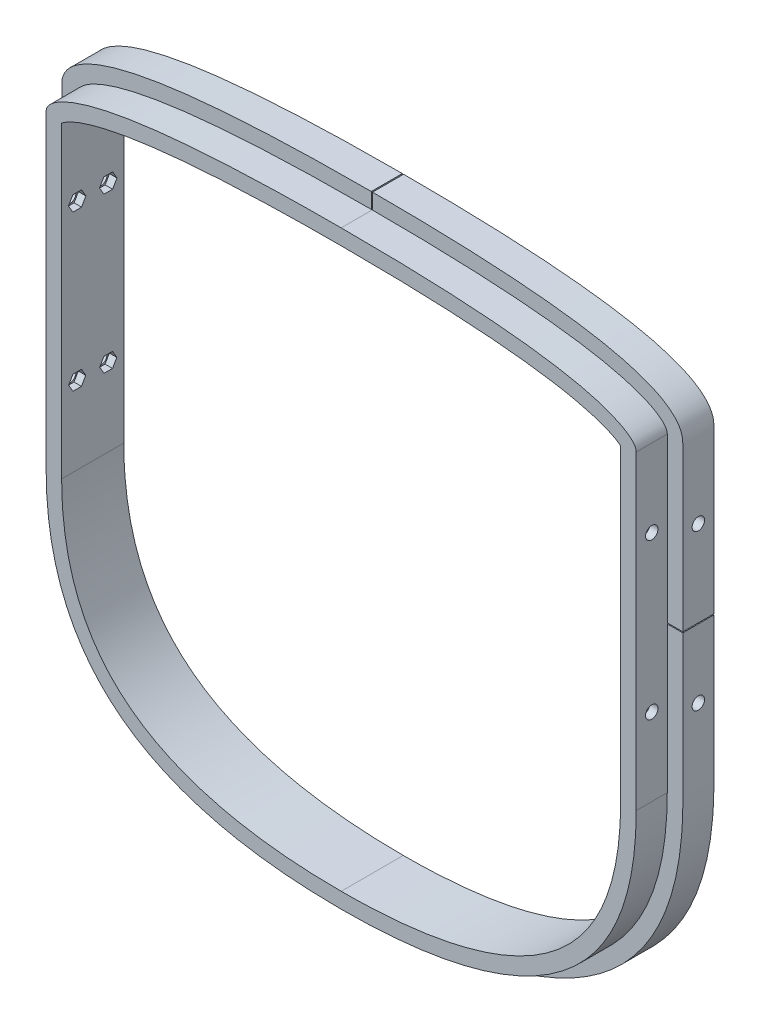
SolidWorks part; units mm, degrees
ref_plane "Front Plane" through (0, 0, 0) normal (0, 0, 1) x (1, 0, 0)
ref_plane "Top Plane" through (0, 0, 0) normal (0, 1, 0) x (1, 0, 0)
ref_plane "Right Plane" through (0, 0, 0) normal (1, 0, 0) x (0, 0, -1)
sketch "Sketch1" plane through (0, 0, 0) normal (0, 0, 1) x (1, 0, 0)
  line L0 (-95, 0) -> (-95, 100) construction
  line L1 (95, 100) -> (95, 0) construction
  line L2 (-95, 0) -> (-95, 100)
  line L3 (95, 100) -> (95, 0)
  line L4 (90, 99.1825) -> (90, 0)
  line L5 (-90, 0) -> (-90, 99.1825)
  line L15 (0.1, -75.1462) -> (-0.3, -75.1462)
  line L16 (-95.145, 47.3605) -> (-95.145, 47.0605)
  line L17 (-100.005, 47.3605) -> (-95.145, 47.3605)
  line L18 (-95.145, 47.0605) -> (-100.005, 47.0605)
  line L19 (-95.145, 47.3605) -> (-95.145, 47.0605)
  line L20 (-100.005, 47.3605) -> (-95.145, 47.3605)
  line L21 (-95.145, 47.0605) -> (-100.005, 47.0605)
  line L22 (-0.3, -75.1462) -> (-0.3, -80.0059)
  line L23 (0.1, -80.006) -> (0.1, -75.1462)
  line L24 (0.1, -75.1462) -> (-0.3, -75.1462)
  line L25 (-0.3, -75.1462) -> (-0.3, -80.0059)
  line L26 (0.1, -80.006) -> (0.1, -75.1462)
  line L28 (-0.3, 115.1456) -> (-0.3, 120.0054)
  line L29 (0.1, 115.1456) -> (-0.3, 115.1456)
  line L30 (0.1, 120.0054) -> (0.1, 115.1456)
  line L31 (-0.3, 115.1456) -> (-0.3, 120.0054)
  line L32 (0.1, 115.1456) -> (-0.3, 115.1456)
  line L33 (0.1, 120.0054) -> (0.1, 115.1456)
  line L41 (95.145, 47.3605) -> (95.145, 47.0605)
  line L42 (95.145, 47.0605) -> (100.005, 47.0605)
  line L43 (100.005, 47.3605) -> (95.145, 47.3605)
  line L44 (95.145, 47.3605) -> (95.145, 47.0605)
  line L45 (95.145, 47.0605) -> (100.005, 47.0605)
  line L46 (100.005, 47.3605) -> (95.145, 47.3605)
  spline S1 degree 3 poles (3136.7113, -2595.1283) (-411.3752, 491.0799) (124.7191, 163.024) (92.6225, -23.0563) (91.0727, -28.5917) (87.718, -36.376) (86.4275, -38.8874) (83.5045, -43.6754) (81.8668, -45.9605) (78.2726, -50.2518) (76.3088, -52.2667) (72.1059, -55.9971) (69.8602, -57.7184) (62.7901, -62.4376) (57.6248, -64.994) (46.8118, -69.0969) (41.1658, -70.649) (29.6492, -72.9887) (23.7792, -73.7773) (-231.7054, -95.489) (-565.5671, 391.7896) (1436.1298, -3777.9141) knots -3.843615 -3.843615 -3.843615 -3.843615 0.125 0.125 0.25 0.25 0.3125 0.3125 0.375 0.375 0.4375 0.4375 0.5 0.5 0.625 0.625 0.75 0.75 0.875 0.875 6.146969 6.146969 6.146969 6.146969 only from (95, 0) to (0, -75) construction
  spline S2 degree 3 poles (-1436.1603, -3777.9993) (565.5714, 391.7943) (231.7065, -95.4891) (-23.7792, -73.7773) (-29.6492, -72.9887) (-41.1658, -70.649) (-46.8118, -69.0969) (-57.6248, -64.994) (-62.7901, -62.4376) (-69.8602, -57.7184) (-72.1059, -55.9971) (-76.3088, -52.2667) (-78.2726, -50.2518) (-81.8668, -45.9605) (-83.5045, -43.6754) (-86.4275, -38.8874) (-87.718, -36.376) (-91.0727, -28.5917) (-92.6225, -23.0563) (-94.0926, -14.5332) (-94.4416, -11.6547) (-94.7819, -7.3036) (-94.9425, -4.4835) (-94.9966, -1.6488) (-95.0143, 6.252) (-94.5075, -6.0366) (-93.6764, 3996.2013) knots -5.146991 -5.146991 -5.146991 -5.146991 0.125 0.125 0.25 0.25 0.375 0.375 0.5 0.5 0.5625 0.5625 0.625 0.625 0.6875 0.6875 0.75 0.75 0.875 0.875 0.9375 0.9375 0.96875 0.998047 0.998047 1.137215 1.137215 1.137215 1.137215 only from (0, -75) to (-95, 0) construction
  spline S3 degree 3 poles (1746.8759, 3647.4615) (-23.1446, -17.0755) (-97.5608, 88.6601) (-94.9009, 100.7509) (-94.8371, 100.9436) (-94.5702, 101.5255) (-94.2605, 101.9807) (-93.3234, 102.955) (-92.7294, 103.4423) (-91.3279, 104.396) (-90.5529, 104.8424) (-88.041, 106.1129) (-86.1831, 106.8394) (-82.3083, 108.1222) (-80.2973, 108.6758) (-74.1487, 110.1566) (-69.9126, 110.9055) (-61.3553, 112.1444) (-57.0295, 112.63) (-48.336, 113.4313) (-43.9687, 113.7455) (-35.2116, 114.2529) (-30.8224, 114.4456) (338.3636, 126.7888) (742.3965, -171.5462) (163.6137, 3990.1333) knots -1.04491 -1.04491 -1.04491 -1.04491 0.015625 0.015625 0.03125 0.03125 0.0625 0.0625 0.09375 0.09375 0.125 0.125 0.1875 0.1875 0.25 0.25 0.375 0.375 0.5 0.5 0.625 0.625 0.75 0.75 11.124038 11.124038 11.124038 11.124038 only from (-95, 100) to (0, 115) construction
  spline S4 degree 3 poles (-163.1607, 3990.1804) (-742.4074, -171.5484) (-338.3648, 126.7888) (30.8224, 114.4456) (35.2116, 114.2529) (43.9687, 113.7455) (48.336, 113.4313) (57.0295, 112.63) (61.3553, 112.1444) (69.9126, 110.9055) (74.1487, 110.1566) (80.2973, 108.6758) (82.3083, 108.1222) (86.1831, 106.8394) (88.041, 106.1129) (90.5529, 104.8424) (91.3279, 104.396) (92.7294, 103.4423) (93.3234, 102.955) (94.2605, 101.9807) (94.5702, 101.5255) (94.8371, 100.9436) (94.9009, 100.7509) (94.9588, 100.4876) (94.974, 100.3949) (94.9895, 100.2502) (94.9971, 100.1551) (94.9998, 100.0573) (95.0006, 99.8105) (94.9809, 121.0154) (94.9385, -3853.5047) knots -10.124077 -10.124077 -10.124077 -10.124077 0.25 0.25 0.375 0.375 0.5 0.5 0.625 0.625 0.75 0.75 0.8125 0.8125 0.875 0.875 0.90625 0.90625 0.9375 0.9375 0.96875 0.96875 0.984375 0.984375 0.992187 0.992187 0.996094 0.999756 0.999756 1.015024 1.015024 1.015024 1.015024 only from (0, 115) to (95, 100) construction
  spline S5 degree 3 poles (95, 0) (95, -5.8637) (94.5826, -11.6922) (92.6225, -23.0563) (91.0727, -28.5917) (87.718, -36.376) (86.4275, -38.8874) (83.5045, -43.6754) (81.8668, -45.9605) (78.2726, -50.2518) (76.3088, -52.2667) (72.1059, -55.9971) (69.8602, -57.7184) (62.7901, -62.4376) (57.6248, -64.994) (46.8118, -69.0969) (41.1658, -70.649) (29.6492, -72.9887) (23.7792, -73.7773) (11.9445, -74.783) (5.9798, -75) (0, -75) knots 0 0 0 0 0.125 0.125 0.25 0.25 0.3125 0.3125 0.375 0.375 0.4375 0.4375 0.5 0.5 0.625 0.625 0.75 0.75 0.875 0.875 1 1 1 1
  spline S6 degree 3 poles (0, -75) (-5.9798, -75) (-11.9445, -74.783) (-23.7792, -73.7773) (-29.6492, -72.9887) (-41.1658, -70.649) (-46.8118, -69.0969) (-57.6248, -64.994) (-62.7901, -62.4376) (-69.8602, -57.7184) (-72.1059, -55.9971) (-76.3088, -52.2667) (-78.2726, -50.2518) (-81.8668, -45.9605) (-83.5045, -43.6754) (-86.4275, -38.8874) (-87.718, -36.376) (-91.0727, -28.5917) (-92.6225, -23.0563) (-94.0926, -14.5332) (-94.4416, -11.6547) (-94.7819, -7.3036) (-94.9425, -4.4835) (-94.9966, -1.6488) (-94.9999, -0.1832) (-95, -0.0953) (-95, 0) knots 0 0 0 0 0.125 0.125 0.25 0.25 0.375 0.375 0.5 0.5 0.5625 0.5625 0.625 0.625 0.6875 0.6875 0.75 0.75 0.875 0.875 0.9375 0.9375 0.96875 0.998047 0.998047 1 1 1 1
  spline S7 degree 3 poles (-95, 100) (-95, 100.2039) (-94.9781, 100.3998) (-94.9009, 100.7509) (-94.8371, 100.9436) (-94.5702, 101.5255) (-94.2605, 101.9807) (-93.3234, 102.955) (-92.7294, 103.4423) (-91.3279, 104.396) (-90.5529, 104.8424) (-88.041, 106.1129) (-86.1831, 106.8394) (-82.3083, 108.1222) (-80.2973, 108.6758) (-74.1487, 110.1566) (-69.9126, 110.9055) (-61.3553, 112.1444) (-57.0295, 112.63) (-48.336, 113.4313) (-43.9687, 113.7455) (-35.2116, 114.2529) (-30.8224, 114.4456) (-17.636, 114.8864) (-8.8222, 115) (0, 115) knots 0 0 0 0 0.015625 0.015625 0.03125 0.03125 0.0625 0.0625 0.09375 0.09375 0.125 0.125 0.1875 0.1875 0.25 0.25 0.375 0.375 0.5 0.5 0.625 0.625 0.75 0.75 1 1 1 1
  spline S8 degree 3 poles (0, 115) (8.8222, 115) (17.636, 114.8864) (30.8224, 114.4456) (35.2116, 114.2529) (43.9687, 113.7455) (48.336, 113.4313) (57.0295, 112.63) (61.3553, 112.1444) (69.9126, 110.9055) (74.1487, 110.1566) (80.2973, 108.6758) (82.3083, 108.1222) (86.1831, 106.8394) (88.041, 106.1129) (90.5529, 104.8424) (91.3279, 104.396) (92.7294, 103.4423) (93.3234, 102.955) (94.2605, 101.9807) (94.5702, 101.5255) (94.8371, 100.9436) (94.9009, 100.7509) (94.9588, 100.4876) (94.974, 100.3949) (94.9895, 100.2502) (94.9971, 100.1551) (94.9998, 100.0573) (95, 100.0064) (95, 100.0087) (95, 100) knots 0 0 0 0 0.25 0.25 0.375 0.375 0.5 0.5 0.625 0.625 0.75 0.75 0.8125 0.8125 0.875 0.875 0.90625 0.90625 0.9375 0.9375 0.96875 0.96875 0.984375 0.984375 0.992187 0.992187 0.996094 0.999756 0.999756 1 1 1 1
  spline S9 degree 1 poles (0, 110) (90, 99.1825) knots 0 0 1 1 construction
  spline S10 degree 1 poles (90, 0) (0, -70) knots 0 0 1 1 construction
  spline S11 degree 1 poles (0, -70) (-90, 0) knots 0 0 1 1 construction
  spline S12 degree 1 poles (-90, 99.1825) (0, 110) knots 0 0 1 1 construction
  spline S13 degree 3 poles (0, 110) (8.1276, 110) (20.3516, 109.8536) (36.5125, 109.2102) (48.5534, 108.436) (58.4634, 107.4683) (66.2506, 106.4099) (71.9725, 105.4481) (76.5934, 104.4569) (80.131, 103.5305) (82.6718, 102.757) (85.0595, 101.9021) (86.8381, 101.1276) (88.0895, 100.4819) (88.8949, 100.0077) (89.4525, 99.6267) (89.8035, 99.3531) (89.9322, 99.2434) (90, 99.1825) knots 0 0 0 0 0.232049 0.348073 0.464097 0.580122 0.638134 0.696146 0.754158 0.783164 0.81217 0.841177 0.870183 0.884686 0.899189 0.913692 0.920943 0.928195 0.928195 0.928195 0.928195
  spline S14 degree 3 poles (90, 0) (90, -1.4013) (89.9499, -4.2123) (89.6338, -9.7605) (88.8063, -16.5742) (87.0275, -24.4516) (83.521, -34.3766) (76.8406, -45.3886) (65.1997, -55.6458) (50.7269, -62.8249) (34.5596, -67.2786) (20.3492, -69.1916) (8.7749, -69.8937) (2.9198, -70) (0, -70) knots 0 0 0 0 0.03125 0.0625 0.125 0.1875 0.25 0.375 0.5 0.625 0.75 0.875 0.9375 1 1 1 1
  spline S15 degree 3 poles (0, -70) (-2.9198, -70) (-8.7749, -69.8937) (-20.3492, -69.1916) (-34.5596, -67.2786) (-50.7269, -62.8249) (-65.1997, -55.6458) (-76.8406, -45.3885) (-83.5211, -34.3767) (-87.0274, -24.4515) (-88.8064, -16.5747) (-89.6333, -9.759) (-89.9498, -4.211) (-90, -1.4009) (-90, 0) knots 0 0 0 0 0.0625 0.125 0.25 0.375 0.5 0.625 0.75 0.8125 0.875 0.9375 0.96875 1 1 1 1
  spline S16 degree 3 poles (-90, 99.1825) (-89.9322, 99.2434) (-89.8035, 99.3531) (-89.4525, 99.6267) (-88.8949, 100.0077) (-88.0895, 100.4819) (-86.8381, 101.1276) (-85.0595, 101.9021) (-82.6718, 102.757) (-80.131, 103.5305) (-76.5934, 104.4569) (-71.9725, 105.4481) (-66.2506, 106.4099) (-58.4634, 107.4683) (-48.5534, 108.436) (-36.5125, 109.2102) (-20.3516, 109.8536) (-8.1276, 110) (0, 110) knots 0.071805 0.071805 0.071805 0.071805 0.079057 0.086308 0.100811 0.115314 0.129817 0.158823 0.18783 0.216836 0.245842 0.303854 0.361866 0.419878 0.535903 0.651927 0.767951 1 1 1 1
  spline S18 degree 3 poles (89.2894, -43.9961) (91.0924, -40.6251) (91.1479, -40.5206) (91.2571, -40.3137) (91.42, -40.003) (91.7934, -39.276) (92.1023, -38.6495) (92.7058, -37.3919) (93.0889, -36.5476) (94.1838, -33.998) (94.8411, -32.2758) (96.6159, -27.0485) (97.5366, -23.4826) (98.5817, -18.0301) (98.8743, -16.1936) (99.3549, -12.496) (99.5418, -10.6463) (99.8198, -6.9456) (99.9107, -5.0945) (99.9818, -2.3169) (99.9946, -1.3908) (100.004, 0.4615) (100.0008, 1.3878) (99.9972, 4.1666) (99.9995, 6.019) (100.0011, 9.724) (100.0011, 11.5764) (100.0003, 17.1339) (99.9994, 20.8388) (99.9991, 31.9537) (100.0002, 39.3636) (100.0008, 61.5933) (99.9994, 76.4132) (100.0001, 93.0855) (100.0002, 94.9379) (99.9998, 97.7166) (100.0006, 98.6429) (99.9999, 99.8007) (100.0031, 100.0323) (99.9877, 100.4953) (99.9698, 100.7277) (99.8853, 101.4154) (99.7878, 101.8625) (99.5813, 102.5168) (99.5026, 102.7322) (99.3259, 103.1577) (99.2273, 103.3688) (98.9092, 103.9833) (98.6676, 104.3702) (98.1354, 105.1066) (97.8446, 105.4557) (97.2218, 106.1225) (96.8891, 106.4419) (95.8513, 107.3516) (95.1114, 107.8916) (93.9523, 108.6336) (93.5566, 108.8696) (92.7564, 109.32) (92.352, 109.5348) (90.3124, 110.5653) (88.6243, 111.2523) (85.1828, 112.4675) (83.4252, 112.9926) (79.8891, 113.9339) (78.1085, 114.3523) (74.5282, 115.1082) (72.7277, 115.4458) (67.3202, 116.3691) (63.7018, 116.8707) (56.4467, 117.7168) (52.8099, 118.0606) (45.5242, 118.6449) (41.8739, 118.8861) (34.5781, 119.2834) (30.931, 119.4408) (19.9911, 119.8193) (12.7001, 119.9439) (1.7659, 120.0061) (-1.8785, 120.0058) (-9.1666, 119.9636) (-12.8102, 119.9212) (-23.7398, 119.717) (-31.0244, 119.4775) (-41.9471, 118.8809) (-45.5873, 118.6424) (-52.8658, 118.0566) (-56.5041, 117.7079) (-61.9594, 117.0693) (-63.7791, 116.8375) (-67.4067, 116.3266) (-69.2149, 116.0472) (-72.8175, 115.4287) (-74.6122, 115.091) (-78.1833, 114.3362) (-79.9595, 113.9188) (-83.4862, 112.9727) (-85.2374, 112.4474) (-87.8337, 111.5274) (-88.694, 111.1988) (-90.4015, 110.4845) (-91.2418, 110.1007) (-92.8816, 109.2645) (-93.6826, 108.8131) (-94.8397, 108.0582) (-95.2179, 107.7936) (-95.9574, 107.2344) (-96.3198, 106.9397) (-97.3571, 106.0156) (-97.986, 105.3409) (-98.6504, 104.3835) (-98.777, 104.186) (-99.0122, 103.7852) (-99.1214, 103.5811) (-99.4226, 102.9575) (-99.5886, 102.5267) (-99.7789, 101.8551) (-99.8326, 101.6257) (-99.9172, 101.1674) (-99.9483, 100.9377) (-100.0087, 100.247) (-100.0052, 99.7843) (-99.9986, 98.859) (-100, 98.3965) (-100.0004, 97.4715) (-99.9999, 97.0091) (-100.0002, 94.6966) (-100, 92.8466) (-100, 87.2967) (-100, 76.1969) (-100, 65.0971) (-100, 42.8974) (-100, 28.0976) (-100, 9.5979) (-99.9994, 5.898) (-100, 1.2731) (-100.0018, 0.3481) (-99.9938, -1.5019) (-99.9804, -2.4272) (-99.9053, -5.1961) (-99.8127, -7.0353) (-99.3966, -12.5309) (-98.9349, -16.1653) (-97.5636, -23.3627) (-96.6555, -26.926) (-94.8697, -32.2035) (-94.2095, -33.9324) (-92.7581, -37.3147) (-91.9659, -38.9698) (-89.3854, -43.825) (-87.3956, -46.916) (-84.5253, -50.5724) (-83.9342, -51.29) (-82.7265, -52.6889) (-82.1088, -53.3719) (-80.2156, -55.3732) (-78.9002, -56.6439) (-74.8049, -60.2787) (-71.8763, -62.4655) (-67.9847, -64.9244) (-67.1949, -65.4025) (-65.5931, -66.3322) (-64.7811, -66.7836) (-62.3319, -68.0889) (-60.6753, -68.8977) (-55.6412, -71.1595) (-52.2001, -72.4492) (-46.9351, -74.1184) (-45.1627, -74.63) (-42.4801, -75.3361) (-41.5819, -75.5613) (-39.7868, -75.99) (-38.8889, -76.1938) (-34.3969, -77.1637) (-30.7968, -77.783) (-23.5862, -78.7748) (-19.9756, -79.1464) (-12.746, -79.6872) (-9.1268, -79.8545) (-1.8815, -80.0215) (1.7446, -80.024) (9.0038, -79.861) (12.6371, -79.6936) (19.9122, -79.1523) (23.5541, -78.7785) (30.8488, -77.7749) (34.4618, -77.1502) (41.6046, -75.6052) (45.1347, -74.6856) (52.094, -72.4867) (55.5231, -71.2071) (59.7297, -69.3235) (60.5684, -68.9318) (62.2292, -68.1218) (63.0509, -67.7037) (65.489, -66.4087) (67.0786, -65.4911) (71.7327, -62.565) (74.6828, -60.3835) (78.1475, -57.3194) (78.8291, -56.6896) (80.156, -55.4072) (80.8029, -54.7532) (82.6937, -52.7522) (83.8881, -51.3668) (87.2805, -47.0622) (89.2894, -43.9961) (91.0924, -40.6251) (91.1479, -40.5206) knots -0.015625 -0.015625 0 0 0.000488 0.000488 0.000977 0.001953 0.003906 0.003906 0.007812 0.007812 0.015625 0.015625 0.03125 0.03125 0.039062 0.039062 0.046875 0.046875 0.054687 0.054687 0.058594 0.058594 0.0625 0.0625 0.070312 0.070312 0.078125 0.078125 0.09375 0.09375 0.125 0.125 0.1875 0.1875 0.195312 0.195312 0.199219 0.199219 0.200195 0.200195 0.201172 0.201172 0.203125 0.203125 0.204102 0.204102 0.205078 0.205078 0.207031 0.207031 0.208984 0.208984 0.210937 0.210937 0.214844 0.214844 0.216797 0.216797 0.21875 0.21875 0.226562 0.226562 0.234375 0.234375 0.242187 0.242187 0.25 0.25 0.265625 0.265625 0.28125 0.28125 0.296875 0.296875 0.3125 0.3125 0.34375 0.34375 0.359375 0.359375 0.375 0.375 0.40625 0.40625 0.421875 0.421875 0.4375 0.4375 0.445312 0.445312 0.453125 0.453125 0.460937 0.460937 0.46875 0.46875 0.476562 0.476562 0.480469 0.480469 0.484375 0.484375 0.488281 0.488281 0.490234 0.490234 0.492187 0.492187 0.496094 0.496094 0.49707 0.49707 0.498047 0.498047 0.5 0.5 0.500977 0.500977 0.501953 0.501953 0.503906 0.503906 0.505859 0.505859 0.507812 0.507812 0.515625 0.515625 0.53125 0.5625 0.5625 0.625 0.625 0.640625 0.640625 0.644531 0.644531 0.648437 0.648437 0.65625 0.65625 0.671875 0.671875 0.6875 0.6875 0.695312 0.695312 0.703125 0.703125 0.71875 0.71875 0.722656 0.722656 0.726562 0.726562 0.734375 0.734375 0.75 0.75 0.753906 0.753906 0.757812 0.757812 0.765625 0.765625 0.78125 0.78125 0.789062 0.789062 0.792969 0.792969 0.796875 0.796875 0.8125 0.8125 0.828125 0.828125 0.84375 0.84375 0.859375 0.859375 0.875 0.875 0.890625 0.890625 0.90625 0.90625 0.921875 0.921875 0.9375 0.9375 0.941406 0.941406 0.945312 0.945312 0.953125 0.953125 0.96875 0.96875 0.972656 0.972656 0.976562 0.976562 0.984375 0.984375 1 1 1.000488 1.000488 1.000977 only from (91.0378, -40.7273) to (91.0378, -40.7273)
  spline S19 degree 3 poles (89.2894, -43.9961) (91.0924, -40.6251) (91.1479, -40.5206) (91.2571, -40.3137) (91.42, -40.003) (91.7934, -39.276) (92.1023, -38.6495) (92.7058, -37.3919) (93.0889, -36.5476) (94.1838, -33.998) (94.8411, -32.2758) (96.6159, -27.0485) (97.5366, -23.4826) (98.5817, -18.0301) (98.8743, -16.1936) (99.3549, -12.496) (99.5418, -10.6463) (99.8198, -6.9456) (99.9107, -5.0945) (99.9818, -2.3169) (99.9946, -1.3908) (100.004, 0.4615) (100.0008, 1.3878) (99.9972, 4.1666) (99.9995, 6.019) (100.0011, 9.724) (100.0011, 11.5764) (100.0003, 17.1339) (99.9994, 20.8388) (99.9991, 31.9537) (100.0002, 39.3636) (100.0008, 61.5933) (99.9994, 76.4132) (100.0001, 93.0855) (100.0002, 94.9379) (99.9998, 97.7166) (100.0006, 98.6429) (99.9999, 99.8007) (100.0031, 100.0323) (99.9877, 100.4953) (99.9698, 100.7277) (99.8853, 101.4154) (99.7878, 101.8625) (99.5813, 102.5168) (99.5026, 102.7322) (99.3259, 103.1577) (99.2273, 103.3688) (98.9092, 103.9833) (98.6676, 104.3702) (98.1354, 105.1066) (97.8446, 105.4557) (97.2218, 106.1225) (96.8891, 106.4419) (95.8513, 107.3516) (95.1114, 107.8916) (93.9523, 108.6336) (93.5566, 108.8696) (92.7564, 109.32) (92.352, 109.5348) (90.3124, 110.5653) (88.6243, 111.2523) (85.1828, 112.4675) (83.4252, 112.9926) (79.8891, 113.9339) (78.1085, 114.3523) (74.5282, 115.1082) (72.7277, 115.4458) (67.3202, 116.3691) (63.7018, 116.8707) (56.4467, 117.7168) (52.8099, 118.0606) (45.5242, 118.6449) (41.8739, 118.8861) (34.5781, 119.2834) (30.931, 119.4408) (19.9911, 119.8193) (12.7001, 119.9439) (1.7659, 120.0061) (-1.8785, 120.0058) (-9.1666, 119.9636) (-12.8102, 119.9212) (-23.7398, 119.717) (-31.0244, 119.4775) (-41.9471, 118.8809) (-45.5873, 118.6424) (-52.8658, 118.0566) (-56.5041, 117.7079) (-61.9594, 117.0693) (-63.7791, 116.8375) (-67.4067, 116.3266) (-69.2149, 116.0472) (-72.8175, 115.4287) (-74.6122, 115.091) (-78.1833, 114.3362) (-79.9595, 113.9188) (-83.4862, 112.9727) (-85.2374, 112.4474) (-87.8337, 111.5274) (-88.694, 111.1988) (-90.4015, 110.4845) (-91.2418, 110.1007) (-92.8816, 109.2645) (-93.6826, 108.8131) (-94.8397, 108.0582) (-95.2179, 107.7936) (-95.9574, 107.2344) (-96.3198, 106.9397) (-97.3571, 106.0156) (-97.986, 105.3409) (-98.6504, 104.3835) (-98.777, 104.186) (-99.0122, 103.7852) (-99.1214, 103.5811) (-99.4226, 102.9575) (-99.5886, 102.5267) (-99.7789, 101.8551) (-99.8326, 101.6257) (-99.9172, 101.1674) (-99.9483, 100.9377) (-100.0087, 100.247) (-100.0052, 99.7843) (-99.9986, 98.859) (-100, 98.3965) (-100.0004, 97.4715) (-99.9999, 97.0091) (-100.0002, 94.6966) (-100, 92.8466) (-100, 87.2967) (-100, 76.1969) (-100, 65.0971) (-100, 42.8974) (-100, 28.0976) (-100, 9.5979) (-99.9994, 5.898) (-100, 1.2731) (-100.0018, 0.3481) (-99.9938, -1.5019) (-99.9804, -2.4272) (-99.9053, -5.1961) (-99.8127, -7.0353) (-99.3966, -12.5309) (-98.9349, -16.1653) (-97.5636, -23.3627) (-96.6555, -26.926) (-94.8697, -32.2035) (-94.2095, -33.9324) (-92.7581, -37.3147) (-91.9659, -38.9698) (-89.3854, -43.825) (-87.3956, -46.916) (-84.5253, -50.5724) (-83.9342, -51.29) (-82.7265, -52.6889) (-82.1088, -53.3719) (-80.2156, -55.3732) (-78.9002, -56.6439) (-74.8049, -60.2787) (-71.8763, -62.4655) (-67.9847, -64.9244) (-67.1949, -65.4025) (-65.5931, -66.3322) (-64.7811, -66.7836) (-62.3319, -68.0889) (-60.6753, -68.8977) (-55.6412, -71.1595) (-52.2001, -72.4492) (-46.9351, -74.1184) (-45.1627, -74.63) (-42.4801, -75.3361) (-41.5819, -75.5613) (-39.7868, -75.99) (-38.8889, -76.1938) (-34.3969, -77.1637) (-30.7968, -77.783) (-23.5862, -78.7748) (-19.9756, -79.1464) (-12.746, -79.6872) (-9.1268, -79.8545) (-1.8815, -80.0215) (1.7446, -80.024) (9.0038, -79.861) (12.6371, -79.6936) (19.9122, -79.1523) (23.5541, -78.7785) (30.8488, -77.7749) (34.4618, -77.1502) (41.6046, -75.6052) (45.1347, -74.6856) (52.094, -72.4867) (55.5231, -71.2071) (59.7297, -69.3235) (60.5684, -68.9318) (62.2292, -68.1218) (63.0509, -67.7037) (65.489, -66.4087) (67.0786, -65.4911) (71.7327, -62.565) (74.6828, -60.3835) (78.1475, -57.3194) (78.8291, -56.6896) (80.156, -55.4072) (80.8029, -54.7532) (82.6937, -52.7522) (83.8881, -51.3668) (87.2805, -47.0622) (89.2894, -43.9961) (91.0924, -40.6251) (91.1479, -40.5206) knots -0.015625 -0.015625 0 0 0.000488 0.000488 0.000977 0.001953 0.003906 0.003906 0.007812 0.007812 0.015625 0.015625 0.03125 0.03125 0.039062 0.039062 0.046875 0.046875 0.054687 0.054687 0.058594 0.058594 0.0625 0.0625 0.070312 0.070312 0.078125 0.078125 0.09375 0.09375 0.125 0.125 0.1875 0.1875 0.195312 0.195312 0.199219 0.199219 0.200195 0.200195 0.201172 0.201172 0.203125 0.203125 0.204102 0.204102 0.205078 0.205078 0.207031 0.207031 0.208984 0.208984 0.210937 0.210937 0.214844 0.214844 0.216797 0.216797 0.21875 0.21875 0.226562 0.226562 0.234375 0.234375 0.242187 0.242187 0.25 0.25 0.265625 0.265625 0.28125 0.28125 0.296875 0.296875 0.3125 0.3125 0.34375 0.34375 0.359375 0.359375 0.375 0.375 0.40625 0.40625 0.421875 0.421875 0.4375 0.4375 0.445312 0.445312 0.453125 0.453125 0.460937 0.460937 0.46875 0.46875 0.476562 0.476562 0.480469 0.480469 0.484375 0.484375 0.488281 0.488281 0.490234 0.490234 0.492187 0.492187 0.496094 0.496094 0.49707 0.49707 0.498047 0.498047 0.5 0.5 0.500977 0.500977 0.501953 0.501953 0.503906 0.503906 0.505859 0.505859 0.507812 0.507812 0.515625 0.515625 0.53125 0.5625 0.5625 0.625 0.625 0.640625 0.640625 0.644531 0.644531 0.648437 0.648437 0.65625 0.65625 0.671875 0.671875 0.6875 0.6875 0.695312 0.695312 0.703125 0.703125 0.71875 0.71875 0.722656 0.722656 0.726562 0.726562 0.734375 0.734375 0.75 0.75 0.753906 0.753906 0.757812 0.757812 0.765625 0.765625 0.78125 0.78125 0.789062 0.789062 0.792969 0.792969 0.796875 0.796875 0.8125 0.8125 0.828125 0.828125 0.84375 0.84375 0.859375 0.859375 0.875 0.875 0.890625 0.890625 0.90625 0.90625 0.921875 0.921875 0.9375 0.9375 0.941406 0.941406 0.945312 0.945312 0.953125 0.953125 0.96875 0.96875 0.972656 0.972656 0.976562 0.976562 0.984375 0.984375 1 1 1.000488 1.000488 1.000977 only from (91.0378, -40.7273) to (91.0378, -40.7273)
  dimension "D1" = 5
  dimension "D2" = 0
  dimension "D3" = 0.1
  dimension "D4" = 0.1
  dimension "D5" = 0.1
  dimension "D6" = 0.1
extrude "Boss-Extrude1" add sketch "Sketch1" against normal blind 10 contours L46 S19 L33 L32 L31 L20 L19 L21 L25 L24 L26 L45 L44 S7 S8 L3 S5 S6 L2 | S8 S7 L2 S6 S5 L3 L5 S16 S13 L4 S14 S15 region at (-92.313, 50, 0) region at (2.5285, -77.5741, 0)
extrude "Boss-Extrude2" add sketch "Sketch1<3>" along normal blind 10 contours S8 S7 L2 S6 S5 L3 L5 S16 S13 L4 S14 S15 region at (-92.313, 50, 0)
sketch "Sketch1<3>" plane through (0, 0, 0) normal (0, 0, 1) x (1, 0, 0) same geometry as "Sketch1"
sketch "Sketch2" plane through (-95, 0, 0) normal (-1, 0, 0) x (0, 0, 1)
  line L0 (5, 100) -> (5, 0) construction
  line L1 (10, 100) -> (0, 100) construction
  line L2 (10, 0) -> (0, 0) construction
  circle A0 centre (5, 75) radius 2
  circle A1 centre (5, 25) radius 2
  point P10 (0, 0)
  dimension "D1" = 4
  dimension "D2" = 4
  dimension "D3" = 25
  dimension "D4" = 25
extrude "Cut-Extrude1" cut sketch "Sketch2" against normal through all both and the other way through all
sketch "Sketch3" plane through (-90, 0, 0) normal (1, 0, 0) x (0, 0, -1)
  line L0 (-5, 77.4249) -> (-5, 72.5751) construction
  line L1 (-3.6, 72.5751) -> (-2.2, 75)
  line L2 (-2.2, 75) -> (-3.6, 77.4249)
  line L3 (-3.6, 77.4249) -> (-6.4, 77.4249)
  line L4 (-6.4, 77.4249) -> (-7.8, 75)
  line L5 (-7.8, 75) -> (-6.4, 72.5751)
  line L6 (-6.4, 72.5751) -> (-3.6, 72.5751)
  line L7 (-5, 27.3816) -> (-5, 22.6184) construction
  line L8 (-2.25, 25) -> (-3.625, 27.3816)
  line L9 (-3.625, 27.3816) -> (-6.375, 27.3816)
  line L10 (-6.375, 27.3816) -> (-7.75, 25)
  line L11 (-7.75, 25) -> (-6.375, 22.6184)
  line L12 (-6.375, 22.6184) -> (-3.625, 22.6184)
  line L13 (-3.625, 22.6184) -> (-2.25, 25)
  line L14 (0, 99.1825) -> (0, 0) construction
  line L15 (10, 99.1825) -> (-10, 99.1825) construction
  line L16 (10, 0) -> (-10, 0) construction
  line L17 (5, 77.4249) -> (5, 72.5751) construction
  line L18 (6.4, 72.5751) -> (3.6, 72.5751)
  line L19 (7.8, 75) -> (6.4, 72.5751)
  line L20 (6.4, 77.4249) -> (7.8, 75)
  line L21 (3.6, 77.4249) -> (6.4, 77.4249)
  line L22 (2.2, 75) -> (3.6, 77.4249)
  line L23 (3.6, 72.5751) -> (2.2, 75)
  line L24 (5, 27.3816) -> (5, 22.6184) construction
  line L25 (3.625, 22.6184) -> (2.25, 25)
  line L26 (6.375, 22.6184) -> (3.625, 22.6184)
  line L27 (7.75, 25) -> (6.375, 22.6184)
  line L28 (6.375, 27.3816) -> (7.75, 25)
  line L29 (3.625, 27.3816) -> (6.375, 27.3816)
  line L30 (2.25, 25) -> (3.625, 27.3816)
  circle A0 centre (-5, 75) radius 2.4249 construction
  circle A1 centre (-5, 25) radius 2.3816 construction
  circle A2 centre (5, 75) radius 2.4249 construction
  circle A3 centre (5, 25) radius 2.3816 construction
  dimension "D1" = 5.6
  dimension "D2" = 5.5
extrude "Cut-Extrude4" cut sketch "Sketch3" against normal blind 2.4
extrude "Cut-Extrude5" cut sketch "Sketch3<2>" along normal blind 2.4 from surface starting at face at (90, 73, 5)
sketch "Sketch3<2>" plane through (-90, 0, 0) normal (1, 0, 0) x (0, 0, -1) same geometry as "Sketch3"
sketch "Sketch4" plane through (-92.4, 0, 0) normal (1, 0, 0) x (0, 0, -1)
  line L0 (2.2, 75) -> (7.8, 75) construction
  line L4 (2.25, 25) -> (7.75, 25) construction
  circle A0 centre (5, 75) radius 2
  circle A2 centre (5, 25) radius 2
  dimension "D1" = 4
  dimension "D2" = 4
extrude "Cut-Extrude6" cut sketch "Sketch4" against normal through all both and the other way through all
